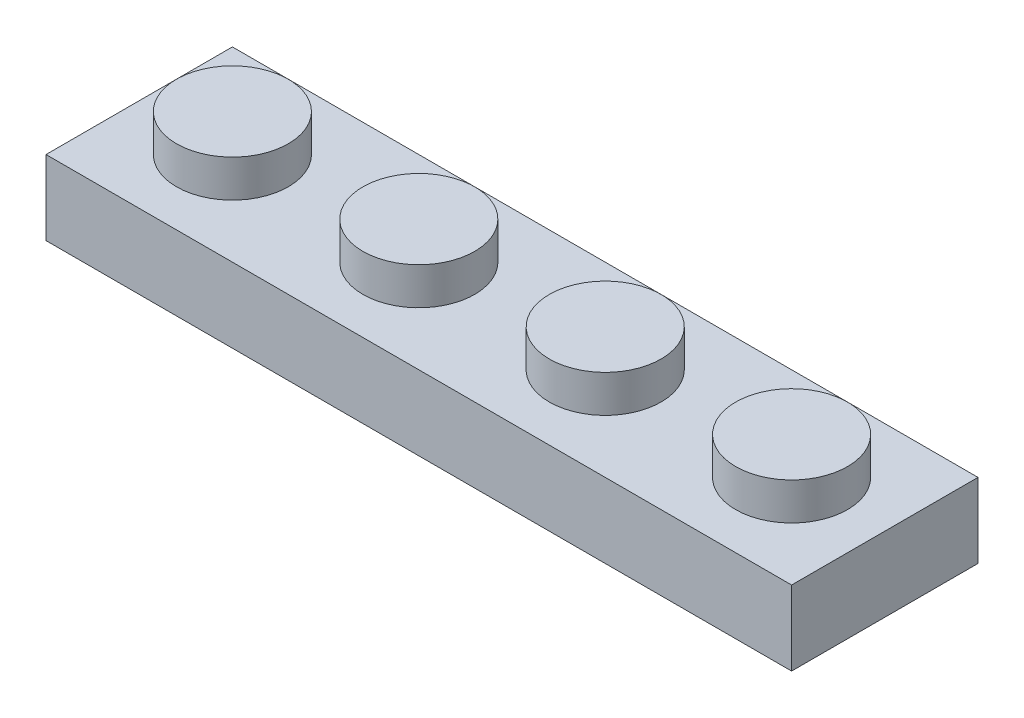
SolidWorks part; units mm, degrees
ref_plane "Front Plane" through (0, 0, 0) normal (0, 0, 1) x (1, 0, 0)
ref_plane "Top Plane" through (0, 0, 0) normal (0, 1, 0) x (1, 0, 0)
ref_plane "Right Plane" through (0, 0, 0) normal (1, 0, 0) x (0, 0, -1)
sketch "Sketch1" plane through (0, 0, 0) normal (0, 1, 0) x (1, 0, 0)
  line L0 (-7.5, 0) -> (-2.5, 0)
  line L1 (-10, -2.5) -> (10, -2.5)
  line L2 (-10, -2.5) -> (-10, 2.5)
  line L3 (-10, 2.5) -> (10, 2.5)
  line L4 (10, -2.5) -> (10, 2.5)
  line L5 (-10, -2.5) -> (10, 2.5) construction
  line L6 (-10, 2.5) -> (10, -2.5) construction
  line L7 (-9, -1.5) -> (9, -1.5)
  line L8 (-9, -1.5) -> (-9, 1.5)
  line L9 (-9, 1.5) -> (9, 1.5)
  line L10 (9, -1.5) -> (9, 1.5)
  line L11 (-9, -1.5) -> (9, 1.5) construction
  line L12 (-9, 1.5) -> (9, -1.5) construction
  circle A0 centre (-7.5, 0) radius 1.5
  circle A1 centre (-7.5, 0) radius 0.75
  circle A2 centre (-2.5, 0) radius 0.75
  circle A3 centre (-2.5, 0) radius 1.5
  circle A4 centre (2.5, 0) radius 0.75
  circle A5 centre (2.5, 0) radius 1.5
  circle A6 centre (7.5, 0) radius 0.75
  circle A7 centre (7.5, 0) radius 1.5
  circle A8 centre (-5, 0) radius 1
  circle A9 centre (0, 0) radius 1
  circle A10 centre (5, 0) radius 1
  point P0 (0, 0)
  point P9 (0, 0)
  dimension "D4" = 3
  dimension "D6" = 1.5
  dimension "D1" = 5
  dimension "D2" = 20
  dimension "D3" = 2.5
  dimension "D5" = 2.5
  dimension "D7" = 1
  dimension "D8" = 1
  dimension "D9" = 4
  dimension "D10" = 3
extrude "Boss-Extrude1" add sketch "Sketch1" along normal blind 2 contours A1 A0 | A1 | A2 | A3 A2 | A4 | A5 A4 | A7 A6 | A6 region at (-6.4693, 0, 1.0307) region at (-8.2288, 0, 0) region at (-2.5, 0, -0.7288) region at (-3.5307, 0, -1.0307) region at (3.5307, 0, -1.0307) region at (8.5307, 0, -1.0307) region at (2.5, 0, 0) region at (7.5, 0, 0)
extrude "Boss-Extrude2" add sketch "Sketch1<3>" along normal blind 1 contours L2 L3 L4 L1
sketch "Sketch1<3>" plane through (0, 0, 0) normal (0, 1, 0) x (1, 0, 0) same geometry as "Sketch1"
extrude "Cut-Extrude1" cut sketch "Sketch1<4>" along normal blind 1 contours A1 | A2 | A4 | A6 region at (-8.2288, 0, 0) region at (-2.5, 0, -0.7288) region at (2.5, 0, 0) region at (7.5, 0, 0)
sketch "Sketch1<4>" plane through (0, 0, 0) normal (0, 1, 0) x (1, 0, 0) same geometry as "Sketch1"
extrude "Boss-Extrude3" add sketch "Sketch1<5>" against normal blind 1 contours L1 L4 L3 L2 L10 L7 L8 L9 | L0 A8 | L0 A8 | A9 | A10 region at (-5, 0, -0.4244) region at (-5, 0, 0.4244) region at (0, 0, 0) region at (5, 0, 0) region at (-9.7938, 0, 0)
sketch "Sketch1<5>" plane through (0, 0, 0) normal (0, 1, 0) x (1, 0, 0) same geometry as "Sketch1"
